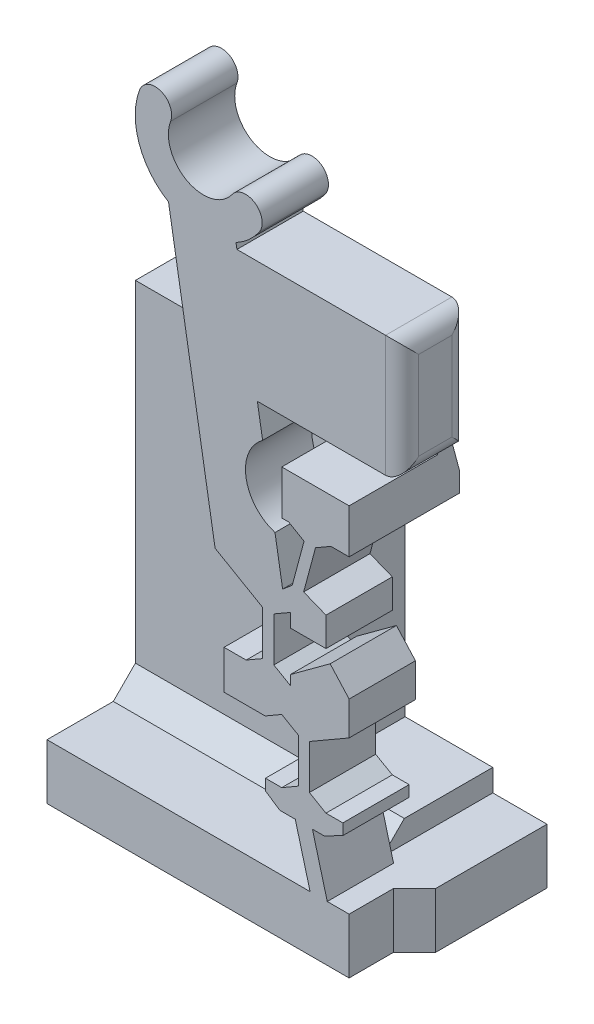
SolidWorks part; units mm, degrees
material "Nylon 6/12"
ref_plane "Front Plane" through (0, 0, 0) normal (0, 0, 1) x (1, 0, 0)
ref_plane "Top Plane" through (0, 0, 0) normal (0, 1, 0) x (1, 0, 0)
ref_plane "Right Plane" through (0, 0, 0) normal (1, 0, 0) x (0, 0, -1)
sketch "Sketch-SkeletonConfigUp" plane through (0, 0, 0) normal (0, 0, 1) x (1, 0, 0)
  line L0 (0, 0) -> (0, -50000) construction
  line L1 (0, 0) -> (4.5811, 6.2164) construction
  line L2 (9.8143, 13.3177) -> (4.5811, 13.945) construction
  line L3 (4.5811, 13.945) -> (2.9713, 10.4094) construction
  line L4 (2.9713, 10.4094) -> (4.5811, 6.2164) construction
  line L5 (4.5811, 13.945) -> (6.2429, 19.1409) construction
  line L6 (2.9713, 10.4094) -> (0.0405, 27.8193) construction
  line L7 (4.5811, 6.2164) -> (9.8143, 13.3177) construction
  line L8 (-587.3593, -797.0242) -> (9.8143, 13.3177) construction
  dimension "D2" = 7.7221
  dimension "D3" = 8.8212
  dimension "D4" = 5.2707
  dimension "D5" = 119.553
  dimension "D6" = 3.8848
  dimension "D7" = 5.4552
  dimension "D8" = 17.6549
  dimension "D9" = 4.4914
  dimension "D10" = 6.745
  dimension "D11" = 145.964
  dimension "D12" = 143.612
sketch "Sketch-SkeletonConfigDown" plane through (0, 0, 0) normal (0, 0, 1) x (1, 0, 0)
  line L0 (0, 0) -> (0, -50000) construction
  line L1 (0, 0) -> (4.5811, 6.2164) construction
  line L2 (9.8143, 13.3177) -> (4.5811, 13.945) construction
  line L3 (4.5811, 13.945) -> (6.1909, 10.4094) construction
  line L4 (6.1909, 10.4094) -> (4.5811, 6.2164) construction
  line L5 (4.5811, 13.945) -> (1.753, 18.6098) construction
  line L6 (6.1909, 10.4094) -> (-8.8652, 19.6294) construction
  line L7 (4.5811, 6.2164) -> (9.8143, 13.3177) construction
  line L8 (-589.9357, -800.5203) -> (9.8143, 13.3177) construction
  dimension "D2" = 7.7221
  dimension "D3" = 8.8212
  dimension "D4" = 5.2707
  dimension "D5" = 119.553
  dimension "D6" = 3.8848
  dimension "D7" = 5.4552
  dimension "D8" = 17.6549
  dimension "D9" = 4.4914
  dimension "D10" = 6.745
  dimension "D11" = 145.964
  dimension "D1" = 143.612
ref_plane "Plane-Cam Base" through (9.128, 0, 0) normal (1, 0, 0) x (0, 0, -1)
ref_plane "Plane-Down-to-Up Derailleur Clearance" through (6.628, 0, 0) normal (1, 0, 0) x (0, 0, -1)
ref_plane "Plane-Cam Cavity Roof" through (5.128, 0, 0) normal (1, 0, 0) x (0, 0, -1)
sketch "Sketch-SwitchBossUp" plane through (0, 0, 0) normal (0, 0, 1) x (1, 0, 0)
  line L0 (3.5811, 11.4759) -> (3.5811, 12.945) construction
  line L5 (5.5811, 12.5419) -> (5.5811, 11.2301)
  line L7 (1.5115, 25.1048) -> (1.5536, 24.8548)
  line L8 (-0.4607, 24.7728) -> (1.6885, 12.0057) construction
  line L9 (2.9713, 10.4094) -> (0.0405, 27.8193) construction
  line L11 (0.1364, 21.2256) -> (2.1086, 21.5576) construction
  line L15 (6.628, -23.7286) -> (6.628, 23.7286) construction
  line L16 (2.9713, 10.4094) -> (4.5811, 6.2164) construction
  line L17 (3.5811, 12.945) -> (3.5811, 14.945) construction
  line L18 (5.5811, 12.945) -> (5.5811, 14.945) construction
  line L19 (4.3311, 13.945) -> (4.8311, 13.945) construction
  line L20 (3.5811, 14.945) -> (5.5811, 14.945) construction
  line L21 (3.5811, 12.945) -> (5.5811, 12.945) construction
  line L22 (4.5811, 12.945) -> (4.5811, 14.945) construction
  line L23 (4.5811, 6.2164) -> (8.4851, 7.1236) construction
  line L24 (1.9713, 9.4094) -> (1.9713, 11.4094) construction
  line L25 (3.9713, 9.4094) -> (3.9713, 11.4094) construction
  line L26 (3.9713, 9.4094) -> (1.9713, 9.4094) construction
  line L27 (1.9713, 11.4094) -> (3.9713, 11.4094) construction
  line L28 (3.5811, 7.2164) -> (5.5811, 7.2164) construction
  line L29 (3.5811, 7.2164) -> (3.5811, 5.2164) construction
  line L30 (5.5811, 7.2164) -> (5.5811, 5.2164) construction
  line L31 (3.5811, 5.2164) -> (5.5811, 5.2164) construction
  line L32 (4.8311, 6.2164) -> (4.3311, 6.2164) construction
  line L40 (3.2213, 10.4094) -> (2.7213, 10.4094) construction
  line L66 (0.0405, 27.8193) -> (0.0405, 50027.8193) construction
  line L75 (4.5811, 3.8504) -> (5.251, 1.3504) construction
  line L76 (5.5811, 11.2301) -> (5.5811, 12.5419) construction
  line L77 (5.5811, 7.6494) -> (6.628, 8.2538)
  line L80 (5.7703, 10.7301) -> (6.628, 9.7776)
  line L81 (9.128, 1033.2419) -> (9.128, 20.0586) construction
  line L85 (6.8754, 9.5028) -> (8.4993, 7.6992) construction
  line L88 (5.6391, 17.348) -> (6.628, 17.348)
  line L92 (3.7762, 8.3129) -> (6.8754, 9.5028) construction
  line L98 (1.9713, 8.9764) -> (0.9713, 8.9764)
  line L99 (0.9713, 8.9764) -> (0.9713, 7.2164)
  line L100 (0.9713, 7.2164) -> (2.8311, 7.2164)
  line L101 (4.5811, 6.2164) -> (6.8754, 9.5028) construction
  line L103 (0.0405, 27.8193) -> (1.9448, 26.4638) construction
  line L104 (6.8754, 9.5028) -> (8.4993, 7.6992) construction
  line L107 (1.9713, 9.4094) -> (1.9713, 8.9764) construction
  line L109 (0.0405, 27.8193) -> (-2.1498, 28.6358) construction
  line L111 (6.628, 9.7776) -> (6.628, 8.2538)
  line L112 (6.628, 9.7776) -> (6.8754, 9.5028) construction
  line L113 (2.8441, 4.7834) -> (2.8441, 4.2834)
  line L114 (7.3693, 7.7363) -> (7.3563, 7.7363) construction
  line L121 (5.6392, -1.1725) -> (5.6392, 1.3504) construction
  line L122 (9.028, 22.3681) -> (9.028, 19.3681)
  line L127 (5.5811, 15.3347) -> (5.5811, 14.945) construction
  line L133 (2.9713, 10.4094) -> (6.1909, 10.4094) construction
  line L134 (4.5811, 10.4094) -> (4.5811, 13.945) construction
  line L135 (4.5811, 10.4094) -> (4.5811, 6.2164) construction
  line L137 (3.9713, 9.4094) -> (5.5811, 7.2164) construction
  line L139 (5.7703, 10.7301) -> (3.9713, 9.4094)
  line L142 (2.948, 1.3504) -> (2.948, -1.152)
  line L143 (9.128, 20.0586) -> (9.128, 18.3333) construction
  line L145 (9.128, 16.6071) -> (9.128, -49992.4167) construction
  line L147 (5.5811, 11.2301) -> (5.5811, 12.5419) construction
  line L150 (2.948, -1.152) -> (6.628, -1.152)
  line L151 (4.1929, 3.8504) -> (4.9694, 3.8504) construction
  line L152 (4.5902, 14.945) -> (4.0543, 12.945)
  line L153 (5.1078, 14.945) -> (4.572, 12.945)
  line L157 (3.5811, 17.348) -> (3.5811, 15.348)
  line L158 (5.8059, 15.348) -> (6.628, 15.348)
  line L162 (3.2213, 11.4094) -> (3.2213, 9.4094)
  line L164 (2.7213, 11.4094) -> (2.7213, 9.4094)
  line L169 (4.3311, 7.2164) -> (4.3311, 5.2164)
  line L170 (4.8311, 5.2164) -> (4.8311, 7.2164)
  line L175 (4.3311, 7.2164) -> (3.5811, 7.6494)
  line L176 (4.8311, 7.2164) -> (5.5811, 7.6494)
  line L177 (5.5811, 7.2164) -> (5.5811, 7.6494) construction
  line L179 (4.3311, 5.2164) -> (3.5811, 4.7834)
  line L180 (3.5811, 5.2164) -> (3.5811, 4.7834) construction
  line L181 (3.5811, 4.7834) -> (2.8441, 4.7834)
  line L183 (4.8311, 5.2164) -> (5.5811, 4.7834)
  line L184 (5.5811, 5.2164) -> (5.5811, 4.7834) construction
  line L186 (9.128, -23.7286) -> (9.128, 23.7286) construction
  line L187 (2.7213, 9.4094) -> (1.9713, 8.9764)
  line L188 (3.2213, 9.4094) -> (3.9713, 8.9764)
  line L189 (3.2213, 11.4094) -> (3.9713, 11.8424)
  line L190 (2.7213, 11.4094) -> (1.6885, 12.0057)
  line L191 (3.9713, 11.4094) -> (3.9713, 11.8424) construction
  line L192 (3.9713, 11.8424) -> (3.9713, 11.2301)
  line L193 (4.572, 12.945) -> (5.5811, 12.5419)
  line L194 (4.0543, 12.945) -> (3.6203, 12.5779)
  line L195 (3.9713, 11.2301) -> (5.5811, 11.2301)
  line L196 (3.9713, 9.4094) -> (3.9713, 8.9764)
  line L197 (3.5811, 7.2164) -> (3.5811, 7.6494) construction
  line L199 (3.5811, 7.6494) -> (2.8311, 7.2164)
  line L201 (2.8441, 4.2834) -> (2.8441, 3.8504) construction
  line L202 (2.8441, 3.8504) -> (4.1929, 3.8504) construction
  line L205 (4.1929, 3.8504) -> (3.4985, 3.8504)
  line L207 (9.128, 18.3333) -> (9.128, 16.6071) construction
  line L208 (6.628, -1.152) -> (6.628, 1.3504)
  line L209 (9.128, 20.0586) -> (9.128, 16.6071) construction
  line L211 (5.6392, 1.3504) -> (4.9694, 3.8504)
  line L212 (4.8628, 1.3504) -> (4.1929, 3.8504)
  line L214 (4.5902, 14.945) -> (3.8921, 15.348)
  line L215 (3.8921, 15.348) -> (3.5811, 15.348)
  line L216 (5.1078, 14.945) -> (5.8059, 15.348)
  line L217 (5.5811, 12.945) -> (5.5811, 12.5419) construction
  line L218 (5.1078, 14.945) -> (5.1078, 15.348) construction
  line L219 (5.8059, 15.348) -> (3.8921, 15.348) construction
  line L221 (9.028, 22.3681) -> (9.028, 24.8548)
  line L224 (3.5811, 17.348) -> (5.6391, 17.348)
  line L232 (6.628, 15.348) -> (6.628, 17.348)
  line L236 (1.5536, 24.8548) -> (9.028, 24.8548)
  line L240 (4.9694, 3.8504) -> (5.4959, 3.8504)
  line L241 (5.4959, 3.8504) -> (6.3441, 4.2834)
  line L250 (9.028, 19.3681) -> (2.4772, 19.3681)
  line L252 (3.2756, 14.6257) -> (3.6203, 12.5779)
  line L253 (4.3396, 14.0097) -> (4.8226, 13.8803) construction
  line L254 (5.6392, 1.3504) -> (4.8628, 1.3504) construction
  line L255 (4.8628, 1.3504) -> (2.948, 1.3504) construction
  line L256 (4.5811, 6.2164) -> (4.5811, 3.8504) construction
  line L257 (4.8628, 1.3504) -> (2.948, 1.3504)
  line L259 (5.6392, 1.3504) -> (6.628, 1.3504)
  line L260 (3.4985, 3.8504) -> (2.8441, 4.2834)
  line L261 (1.6885, 12.0057) -> (0.5652, 12.6542)
  line L262 (0.5652, 12.6542) -> (-1.5413, 25.1678)
  line L263 (2.4772, 19.3681) -> (2.7152, 17.9544)
  line L266 (1.5536, 24.8548) -> (2.4772, 19.3681) construction
  line L367 (5.5811, 4.7834) -> (6.3441, 4.7834)
  line L368 (6.3441, 4.7834) -> (6.3441, 4.2834)
  arc A0 (1.5115, 25.1048) -> (2.5558, 26.0289) centre (0.0405, 27.8193) ccw
  arc A1 (-1.5413, 25.1678) -> (-2.8525, 28.8978) centre (0.0405, 27.8193) cw
  arc A2 (-2.8525, 28.8978) -> (-1.447, 28.3738) centre (-2.1498, 28.6358) cw
  arc A3 (2.5558, 26.0289) -> (1.3338, 26.8987) centre (1.9448, 26.4638) ccw
  arc A4 (-1.447, 28.3738) -> (1.3338, 26.8987) centre (0.0405, 27.8193) ccw
  arc A5 (3.5811, 12.945) -> (3.5811, 14.945) centre (3.2894, 13.945) ccw construction
  arc A6 (5.5811, 12.945) -> (5.5811, 14.945) centre (5.8727, 13.945) cw construction
  arc A7 (2.607, 9.935) -> (1.9713, 11.4094) centre (1.6796, 10.4094) ccw construction
  arc A8 (3.9713, 11.4094) -> (3.9713, 9.4094) centre (4.2629, 10.4094) ccw construction
  arc A9 (3.5811, 7.2164) -> (3.5811, 5.2164) centre (3.2895, 6.2164) cw construction
  arc A10 (5.5811, 7.2164) -> (5.5811, 5.2164) centre (5.8728, 6.2164) ccw construction
  circle A28 centre (0.0405, 27.8193) radius 2.3375 construction
  arc A29 (1.9713, 9.4094) -> (2.607, 9.935) centre (1.6796, 10.4094) ccw construction
  arc A30 (3.2756, 14.6257) -> (2.7152, 17.9544) centre (3.8249, 16.4297) cw
  arc A31 (-0.4607, 24.7728) -> (-1.5413, 25.1678) centre (0.0405, 27.8193) cw construction
  point P53 (4.5811, 13.945)
  point P63 (2.9713, 10.4094)
  point P93 (1.1225, 21.3916)
  dimension "D23" = 1.5875
  dimension "D24" = 0.75
  dimension "D2" = 2
  dimension "D5" = 2
  dimension "D8" = 42
  dimension "D16" = 42
  dimension "D27" = 120
  dimension "D28" = 120
  dimension "D29" = 120
  dimension "D30" = 120
  dimension "D31" = 120
  dimension "D32" = 120
  dimension "D33" = 120
  dimension "D34" = 120
  dimension "D17" = 0.5
  dimension "D21" = 2
  dimension "D38" = 2
  dimension "D39" = 0.5
  dimension "D40" = 60
  dimension "D41" = 1
  dimension "D42" = 45
  dimension "D43" = 120
  dimension "D10" = 15
  dimension "D25" = 15
  dimension "D26" = 120
  dimension "D35" = 120
  dimension "D83" = 3.5
  dimension "D15" = 0.25
  dimension "D6" = 0.5
  dimension "D13" = 18.5
  dimension "D18" = 2.5
  dimension "D19" = 0.5
  dimension "D20" = 1
  dimension "D12" = 0.75
extrude "Boss-Switch Body" add sketch "Sketch-SwitchBossUp" along normal blind 3
sketch "Sketch1" plane through (0, 0, 0) normal (0, 0, -1) x (-1, 0, 0)
  line L1 (-7.5811, -1.152) -> (0.4122, -1.152)
  line L2 (-7.5811, -1.152) -> (-7.5811, 1.3504)
  line L4 (0.4122, -1.152) -> (0.4122, 1.3504)
  line L5 (-3.5811, 18.848) -> (-7.5811, 18.848)
  line L10 (-7.5811, 18.848) -> (-7.5811, 15.348)
  line L11 (-4.8628, 1.3504) -> (-5.6392, 1.3504)
  line L12 (-7.5811, 15.348) -> (-3.5811, 15.348)
  line L13 (-4.8628, 1.3504) -> (-2.948, 1.3504)
  line L14 (-3.5811, 15.348) -> (-3.5811, 18.848)
  line L20 (-4.9694, 3.8504) -> (-5.6392, 1.3504) construction
  line L22 (-2.948, -1.152) -> (-6.628, -1.152) construction
  line L23 (-2.948, 1.3504) -> (0.4122, 1.3504)
  line L24 (-5.6392, 1.3504) -> (-6.628, 1.3504)
  line L25 (-6.628, 1.3504) -> (-7.5811, 1.3504)
  dimension "D1" = 3.5
extrude "Boss-Flange Width" add sketch "Sketch1" along normal blind 5
ref_plane "Plane-Sta2Sit Groove" through (0.0405, 0, 0) normal (1, 0, 0) x (0, 0, -1)
ref_plane "Plane-Cam Outer Surface" through (-12.0395, 0, 0) normal (1, 0, 0) x (0, 0, -1)
ref_plane "Plane-FlangeTop" through (-7.0395, 0, 0) normal (1, 0, 0) x (0, 0, -1)
sketch "Sketch2" plane through (-7.0395, 0, 0) normal (1, 0, 0) x (0, 0, -1)
  line L0 (5, 15.348) -> (-3, 15.348) construction
  line L1 (5, 17.348) -> (1, 17.348)
  line L2 (5, 17.348) -> (5, 15.348)
  line L3 (5, 15.348) -> (1, 15.348)
  line L4 (1, 17.348) -> (1, 15.348)
  line L5 (-3, -1.152) -> (-3, 1.3504) construction
  line L11 (5, 1.3504) -> (-3, 1.3504)
  line L12 (5, 1.3504) -> (5, -1.152)
  line L13 (5, -1.152) -> (-3, -1.152)
  line L14 (-3, 1.3504) -> (-3, -1.152)
  line L15 (0, 10.4094) -> (0, 27.8193) construction
  line L17 (5, 1.3504) -> (5, -1.152) construction
  line L18 (-3, 1.3504) -> (0, 1.3504) construction
  dimension "D1" = 1
  dimension "D2" = 2
extrude "Boss-Flange Height" add sketch "Sketch2" along normal up to surface (11.6675 mm away)
sketch "Sketch10" plane through (0, 15.348, 0) normal (0, 1, 0) x (1, 0, 0)
  line L0 (9.128, -23.7286) -> (9.128, 23.7286) construction
  line L1 (7.5811, 5) -> (5.128, 5)
  line L2 (7.5811, 5) -> (7.5811, 2)
  line L3 (7.5811, 2) -> (5.128, 2)
  line L5 (4.628, 7) -> (4.628, 1) construction
  line L6 (3.5811, 1) -> (-7.0395, 1) construction
  line L8 (5.128, 5) -> (5.128, 2)
  dimension "D1" = 1
  dimension "D2" = 0.5
  dimension "D3" = 4.5
extrude "Cut-Up-To-Down Derailleur Clearance" cut sketch "Sketch10" along normal up to next
sketch "Sketch17" plane through (0, 15.348, 0) normal (0, -1, 0) x (1, 0, 0)
  line L0 (5.128, -5) -> (-7.0395, -5)
  line L1 (5.128, -5) -> (-7.0395, -5) construction
  line L2 (-7.0395, -5) -> (-7.0395, -1)
  line L3 (-7.0395, -1) -> (5.128, -1)
  line L4 (5.128, -1) -> (5.128, -5)
  line L5 (-7.0395, -1) -> (-7.0395, -5) construction
extrude "Boss-Flange Support" add sketch "Sketch17" along normal up to surface (13.9976 mm away) up to face at (3.5343, 1.3504, 0.2)
sketch "Sketch-HolePositions" plane through (0, -1.152, 0) normal (0, -1, 0) x (1, 0, 0)
  line L0 (-7.0395, -3) -> (7.5811, -3) construction
  line L1 (7.5811, -5) -> (-7.0395, -5) construction
  line L2 (7.5811, -5) -> (7.5811, 0) construction
  line L4 (-7.0395, -22.2167) -> (-7.0395, 22.2167) construction
  point P6 (-5.0395, -3)
  point P7 (-0.5395, -3)
  dimension "D1" = 2
  dimension "D2" = 4.5
  dimension "D3" = 2
sketch "Sketch6" plane through (0, -1.152, 0) normal (0, -1, 0) x (-1, 0, 0)
  point P0 (5.0395, 3)
  point P3 (0.5395, 3)
hole_wizard "Tap Drill for M2x0.4 Tap1" positions "Sketch6" profile "Sketch5" hole size "M2x0.4" standard "ANSI Metric" end condition through all
sketch "Sketch5" plane through (-5.0395, -1.152, -3) normal (1, 0, 0) x (0, 0, -1)
  line L0 (0, 0) -> (0, 30.5378)
  line L1 (0, 30.5378) -> (0.8, 30.5378)
  line L2 (0.8, 30.5378) -> (0.8, 0)
  line L5 (0.8, 0) -> (0, 0)
  line L11 (0, -6.35) -> (0, 107.95) construction
  dimension "Thru Hole Dia." = 1.6
  dimension "Thru Hole Depth" = 30.5378
sketch "Sketch9" plane through (0, -1.152, 0) normal (0, -1, 0) x (1, 0, 0)
  point P0 (-5.0395, -3)
  point P3 (-0.5395, -3)
hole_wizard "M2 Clearance Hole2" positions "Sketch9" profile "Sketch8" hole size "M2" standard "ANSI Metric"
sketch "Sketch8" plane through (-5.0395, -1.152, -3) normal (1, 0, 0) x (0, 0, -1)
  line L0 (0, 0) -> (0, 15.721)
  line L1 (0, 15.721) -> (1.2, 15)
  line L2 (1.2, 15) -> (1.2, 0)
  line L5 (1.2, 0) -> (0, 0)
  line L10 (0, 15.721) -> (-1.2, 15) construction
  line L11 (0, -6.35) -> (0, 107.95) construction
  dimension "Hole Dia." = 2.4
  dimension "Hole Depth" = 15
  dimension "Drill Angle" = 118
sketch "Sketch-Measurements for Derailleur Ramps" [suppressed] plane through (0, 0, 0) normal (0, 0, 1) x (1, 0, 0)
  line L0 (3.184, 15.1695) -> (2.4687, 19.4188)
  line L1 (2.8264, 17.2941) -> (1.8402, 17.1281)
  line L2 (2.9713, 10.4094) -> (0.0405, 27.8193) construction
  line L3 (1.8402, 17.1281) -> (-1.3081, 15.0016)
  line L4 (6.1909, 10.4094) -> (-8.8652, 19.6294) construction
  line L5 (1.8402, 17.1281) -> (2.6012, 12.6077)
  line L6 (2.6012, 12.6077) -> (-1.3081, 15.0016)
  line L7 (0.2661, 16.0649) -> (0.2661, 17.1281)
  line L8 (0.2661, 17.1281) -> (1.8402, 17.1281)
  line L9 (6.1909, 10.4094) -> (2.9713, 10.4094)
  line L10 (5.386, 8.3129) -> (3.7762, 8.3129)
  line L11 (2.6116, 18.5698) -> (1.5115, 25.1048) construction
  line L12 (6.1909, 10.4094) -> (4.5811, 6.2164) construction
  line L13 (4.5811, 8.3129) -> (4.5811, 8.7912)
  line L14 (4.5811, 6.2164) -> (5.386, 8.3129)
  line L15 (2.9713, 10.4094) -> (4.5811, 6.2164) construction
  line L16 (3.7762, 8.3129) -> (4.5811, 6.2164)
  line L17 (5.386, 8.3129) -> (5.386, 8.7912)
  dimension "D1" = 1.5742
  dimension "D2" = 0.8049
ref_plane "Plane1" through (0, 7.1236, 0) normal (0, 1, 0) x (1, 0, 0)
ref_plane "Plane-Cantilever Cut" [suppressed] through (7.0848, 8.5204, -1.9058) normal (-0.6301, -0.7578, 0.1695) x (-0.7765, 0.6151, -0.1368)
sketch "Sketch14" [suppressed] plane through (7.0848, 8.5204, -1.9058) normal (-0.6301, -0.7578, 0.1695) x (-0.7765, 0.6151, -0.1368)
  line L0 (2.3023, -1.6911) -> (-0.3551, -1.6911)
  line L2 (2.3023, -4.3362) -> (2.3023, -1.6911)
  line L3 (-0.3551, -1.6911) -> (-0.3551, -4.4608)
  line L5 (-0.3551, -4.4608) -> (1.0087, -5.0843)
  line L6 (1.0087, -5.0843) -> (2.3023, -4.3362)
extrude "Cut-Down-to-Up Cantilever Slope" [suppressed] cut sketch "Sketch14" against normal up to next
ref_plane "Plane-Symmetry Plane" through (0, 0, 1.5) normal (0, 0, 1) x (1, 0, 0)
sketch "Sketch-Cable Center Point" plane through (0, 0, 1.5) normal (0, 0, 1) x (1, 0, 0)
  line L0 (0.0405, 27.8193) -> (0.1722, 27.0366)
  line L1 (2.9713, 10.4094) -> (0.0405, 27.8193) construction
  point P0 (0.0405, 27.8193)
  dimension "D1" = 0.7937
chamfer "Chamfer-Flange Support" distance 1.5 angle 45 1 edges at (3.5811, 17.348, -3)
chamfer "Chamfer-Flange Support 2" distance 1.5 angle 45 2 edges at (5.128, 17.098, -2) (5.128, 15.348, -1.5)
chamfer "Chamfer-Flange Support 3" distance 1 angle 45 1 edges at (-0.9558, 1.3504, -1)
chamfer "Chamfer7" [suppressed] distance 1 angle 45
sketch "Sketch23" plane through (0, 0, -1) normal (0, 0, 1) x (1, 0, 0)
  line L0 (5.128, 2.3504) -> (1.1605, 2.3504)
  line L1 (-7.0395, 2.3504) -> (5.128, 2.3504) construction
  line L2 (1.1605, 2.3504) -> (1.1605, 13.848)
  line L3 (1.1605, 13.848) -> (5.128, 13.848)
  line L4 (5.128, 13.848) -> (5.128, 2.3504)
  line L5 (0.6605, -1.152) -> (0.6605, 13.848) construction
  dimension "D1" = 0.5
extrude "Cut-Gap for Printing" cut sketch "Sketch23" against normal through all
sketch "Sketch25" plane through (0, 0, 0) normal (0, 0, 1) x (1, 0, 0)
  line L0 (6.628, 15.348) -> (7.5811, 15.348)
  line L1 (7.5811, 15.348) -> (7.5811, 18.848)
  line L2 (7.5811, 18.848) -> (6.628, 18.848)
  line L3 (6.628, -23.7286) -> (6.628, 23.7286) construction
  line L4 (7.5811, 18.848) -> (3.5811, 18.848) construction
  line L5 (6.628, 18.848) -> (6.628, 15.348)
  line L6 (7.5811, 18.848) -> (7.5811, 15.348) construction
extrude "Cut-Derailleur Clearance" cut sketch "Sketch25" against normal through all
chamfer "Chamfer8" distance 1 angle 45 1 edges at (6.628, 0.0992, 0)
ref_plane "Plane2" [suppressed] through (4.8655, 0, -3.2437) normal (-0.8321, 0, 0.5547) x (0.5547, 0, 0.8321)
sketch "Sketch26" [suppressed] plane through (4.8655, 0, -3.2437) normal (-0.8321, 0, 0.5547) x (0.5547, 0, 0.8321)
  line L0 (8.7768, 24.8548) -> (8.7768, 19.0593)
  line L1 (5.0078, 24.8548) -> (0.8618, 24.8548) construction
  line L3 (8.7768, 19.0593) -> (2.8692, 19.0593)
  line L4 (2.8692, 19.0593) -> (2.8692, 24.8548)
  line L5 (2.8692, 24.8548) -> (8.7768, 24.8548)
extrude "Cut-Up-to-Down Cantilever Slope" [suppressed] cut sketch "Sketch26" against normal up to next
sketch "Sketch27" plane through (5.128, 0, 0) normal (1, 0, 0) x (0, 0, -1)
  line L0 (3.5, 18.848) -> (3.5, 13.848) construction
  line L1 (2.5, 18.848) -> (5, 18.848)
  line L2 (2.5, 18.848) -> (2.5, 13.848)
  line L3 (2.5, 13.848) -> (5, 13.848)
  line L4 (5, 18.848) -> (5, 13.848)
  line L5 (3.5, 18.848) -> (5, 18.848) construction
  dimension "D1" = 1
extrude "Cut-Wide Derailleur Clearance" cut sketch "Sketch27" against normal blind 4 and the other way through all
chamfer "Chamfer9" distance 4.5 angle 15 1 edges at (4.8545, 18.848, -2.5) first distance on face at (3.3078, 16.098, -2.5)
sketch "Sketch28" plane through (0, 0, -1) normal (0, 0, 1) x (1, 0, 0)
  line L0 (3.5811, 18.848) -> (6.628, 18.848)
  line L1 (6.628, 18.848) -> (6.628, 17.348)
  line L2 (6.628, 17.348) -> (3.5811, 17.348)
  line L3 (3.5811, 17.348) -> (3.5811, 18.848)
extrude "Cut-Extrude1" cut sketch "Sketch28" along normal up to surface (1 mm away) up to face at (5.1045, 18.098, 0)
fillet "Fillet1" radius 0.75 4 edges at (9.028, 24.8548, 1.5) (9.028, 19.3681, 1.5) (9.028, 22.1115, 3) (9.028, 22.1115, 0)
chamfer "Chamfer10" distance 0.75 angle 60 1 edges at (3.1442, 13.848, -2.5) first distance on face at (3.1442, 13.848, -1.75)
equation "\"axle-diameter\"=2"
equation "\"switch-thickness\"=12"
equation "\"base-width\"=4.0"
equation "\"axle-bushing-radius\"=3"
equation "\"clearance\"= 0.25"
equation "\"arm-width\"=1.5"
equation "\"min-diameter\"=70"
equation "\"alpha\"=143.6120"
equation "\"gamma\"=119.5526"
equation "\"delta\"=145.9637"
equation "\"epsilon\"=6.7452"
equation "\"l_AB\"=8.8212"
equation "\"l_AC\"=4.4914"
equation "\"l_BD\"=5.2707"
equation "\"l_CD\"=3.8848"
equation "\"l_CE\"=17.6549"
equation "\"l_DF\"=5.4552"
equation "\"l_OA\"=7.7221"
equation "\"D2@Sketch-SkeletonConfigUp\" = \"l_OA\""
equation "\"D3@Sketch-SkeletonConfigUp\" = \"l_AB\""
equation "\"D4@Sketch-SkeletonConfigUp\" = \"l_BD\""
equation "\"D5@Sketch-SkeletonConfigUp\" = \"gamma\""
equation "\"D6@Sketch-SkeletonConfigUp\" = \"l_CD\""
equation "\"D7@Sketch-SkeletonConfigUp\" = \"l_DF\""
equation "\"D8@Sketch-SkeletonConfigUp\" = \"l_CE\""
equation "\"D9@Sketch-SkeletonConfigUp\" = \"l_AC\""
equation "\"D_groove\"=3.175"
equation "\"D7@Sketch-SkeletonConfigDown\" = \"l_DF\""
equation "\"D6@Sketch-SkeletonConfigDown\" = \"l_CD\""
equation "\"D2@Sketch-SkeletonConfigDown\" = \"l_OA\""
equation "\"D3@Sketch-SkeletonConfigDown\" = \"l_AB\""
equation "\"D9@Sketch-SkeletonConfigDown\" = \"l_AC\""
equation "\"D8@Sketch-SkeletonConfigDown\" = \"l_CE\""
equation "\"D5@Sketch-SkeletonConfigDown\" = \"gamma\""
equation "\"D4@Sketch-SkeletonConfigDown\" = \"l_BD\""
equation "\"D1@Sketch-SkeletonConfigDown\" = \"alpha\""
equation "\"hinge_length\"=1.5"
equation "\"hinge_depth\"=0.25"
equation "\"D10@Sketch-SkeletonConfigUp\"=\"epsilon\""
equation "\"D11@Sketch-SkeletonConfigUp\"=\"delta\""
equation "\"D12@Sketch-SkeletonConfigUp\"=\"alpha\""
equation "\"D11@Sketch-SkeletonConfigDown\"=\"delta\""
equation "\"D10@Sketch-SkeletonConfigDown\"=\"epsilon\""
equation "\"EE_dx\"=8.9056"
equation "\"EE_dy\"=8.1898"
equation "\"r_groove\"=\"D_groove\"/2"
equation "\"t_wall\"=25.4/16"
equation "\"width_lower\"=\"D_groove\"+\"t_wall\""
equation "\"cable_to_bottom\"=30.6257"
equation "\"switch_EE-up_base_dy\"=24"
equation "\"switch_EE-down_base_dy\"=16"
equation "\"D_axle\"=25.4/8"
equation "\"D_up_to_down\"=16"
equation "\"D_down_to_up\"=25"
equation "\"t_cam_base\"=7.5"
equation "\"D23@Sketch-SwitchBossUp\"=\"D_groove\"/2"
equation "\"D1@Sketch-Cable Center Point\"=\"D_groove\"/4"
